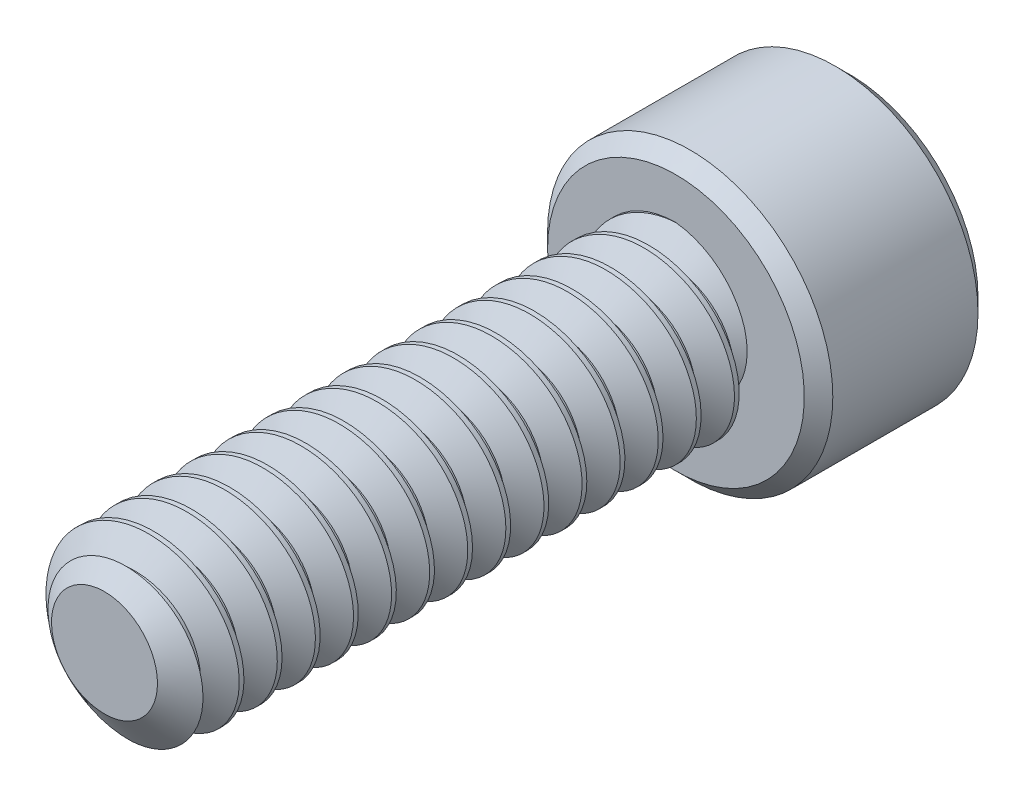
SolidWorks part; units mm, degrees
other "DetailItem1"
ref_plane "Front Plane" through (0, 0, 0) normal (0, 0, 1) x (1, 0, 0)
ref_plane "Top Plane" through (0, 0, 0) normal (0, 1, 0) x (1, 0, 0)
ref_plane "Right Plane" through (0, 0, 0) normal (1, 0, 0) x (0, 0, -1)
sketch "Sketch1" plane through (0, 0, 0) normal (0, 0, 1) x (1, 0, 0)
  circle A0 centre (0, 0) radius 2.413
  dimension "OD" = 4.826
extrude "Extrude1" add sketch "Sketch1" against normal blind 15.875
sketch "Sketch2" plane through (0, 0, 0) normal (0, 0, 1) x (1, 0, 0)
  circle A0 centre (0, 0) radius 2.413 construction
  circle A1 centre (0, 0) radius 2.413
curve "Helix/Spiral1" pitch 1.0583 height 16.9333 turns 16 parameters "pitch"=1.0583
sketch "Sketch3" plane through (0, 0, 0) normal (1, 0, 0) x (0, 0, -1)
  line L0 (-0.926, 2.413) -> (-0.5292, 1.7256)
  line L1 (-0.5292, 1.7256) -> (-0.3969, 1.7256)
  line L2 (-0.3969, 1.7256) -> (0, 2.413)
  line L3 (-0.926, 2.413) -> (0, 2.413)
  line L4 (-0.463, 2.413) -> (-0.463, 1.7256) construction
  line L5 (-0.7276, 2.0693) -> (-0.1984, 2.0693) construction
  line L6 (0, 2.413) -> (0, -2.413) construction
  dimension "D1" = 0.1323
  dimension "D2" = 0.5292
  dimension "D3" = 60
sweep "Cut-Sweep1" cut profiles "Sketch3" path "Helix/Spiral1"
sketch "Sketch4" plane through (0, 0, 0) normal (1, 0, 0) x (0, 0, -1)
  line L0 (0.6592, 2.413) -> (0, 1.4716)
  line L1 (0, 1.4716) -> (0, 2.413)
  line L2 (0.6592, 2.413) -> (0, 2.413)
  line L3 (-0.926, 2.413) -> (0, 2.413) construction
  line L4 (0, 0) -> (7.0209, 0) construction
  dimension "D1" = 55
  dimension "D2" = 0.254
revolve "Cut-Revolve1" cut sketch "Sketch4" angle 360 about L4
sketch "Sketch6" plane through (0, 0, -15.875) normal (0, 0, -1) x (-1, 0, 0)
  circle A0 centre (0, 0) radius 3.9624
  dimension "head dia" = 7.9248
extrude "Extrude2" add sketch "Sketch6" along normal blind 4.826
sketch "Sketch7" plane through (0, 0, -20.701) normal (0, 0, -1) x (-1, 0, 0)
  line L1 (0, 2.2914) -> (-1.9844, 1.1457)
  line L2 (-1.9844, 1.1457) -> (-1.9844, -1.1457)
  line L3 (-1.9844, -1.1457) -> (0, -2.2914)
  line L4 (0, -2.2914) -> (1.9844, -1.1457)
  line L5 (1.9844, -1.1457) -> (1.9844, 1.1457)
  line L6 (1.9844, 1.1457) -> (0, 2.2914)
  circle A0 centre (0, 0) radius 1.9844 construction
  dimension "hex dia" = 3.9688
extrude "Cut-Extrude1" cut sketch "Sketch7" against normal blind 2.9766
sketch "Sketch8" plane through (0, 0, -20.701) normal (0, 0, -1) x (-1, 0, 0)
  circle A0 centre (0, 0) radius 2.2914
extrude "Cut-Extrude2" cut sketch "Sketch8" against normal through all draft 45
chamfer "Chamfer1" distance 0.3962 angle 45 2 edges at (-3.9624, 0, -20.701) (-3.9624, 0, -15.875)
sketch "Sketch10" plane through (0, 0, -15.875) normal (0, 0, 1) x (1, 0, 0)
  circle A1 centre (0, 0) radius 2.413
  circle A2 centre (0, 0) radius 2.413
  dimension "D1" = 0
ref_plane "Plane1" through (0, 0, -31.75) normal (0, 0, 1) x (1, 0, 0)
extrude "partial thread" [suppressed] add sketch "Sketch10" along normal up to surface (12.7 mm away) separate body
chamfer "Chamfer2" [suppressed] distance 0.0965 angle 45
combine bodies "Combine1" [suppressed] operation type add bodies to combine 107 108
sketch "Sketch9" plane through (0, 0, 0) normal (1, 0, 0) x (0, 0, -1)
  line L0 (0, 2.413) -> (0, -2.413) construction
  line L1 (2.6458, 2.413) -> (2.6458, -2.413) construction
  dimension "D1" = 2.6458
equation "\"D3@Helix/Spiral1\" = \"screw length@Extrude1\"+\"pitch@Helix/Spiral1\""
equation "\"D1@Sketch3\" = \"pitch@Helix/Spiral1\"*.125"
equation "\"D2@Sketch3\" = \"pitch@Helix/Spiral1\"*.5"
equation "\"D1@Cut-Extrude1\" = \"hex dia@Sketch7\"*.75"
equation "\"D1@Chamfer1\" = \"head dia@Sketch6\"*.05"
equation "\"D1@Sketch9\" = \"pitch@Helix/Spiral1\"*2.5"
equation "\"D1@Chamfer2\"=\"OD@Sketch1\"*.02"
